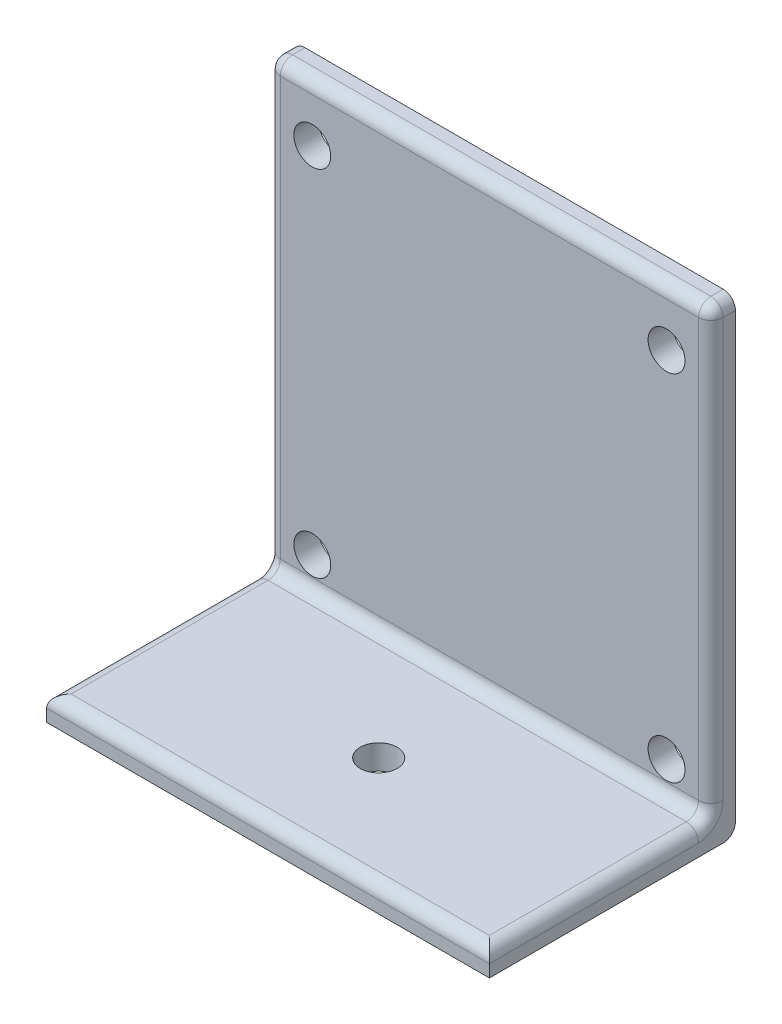
SolidWorks part; units mm, degrees
ref_plane "Front Plane" through (0, 0, 0) normal (0, 0, 1) x (1, 0, 0)
ref_plane "Top Plane" through (0, 0, 0) normal (0, 1, 0) x (1, 0, 0)
ref_plane "Right Plane" through (0, 0, 0) normal (1, 0, 0) x (0, 0, -1)
sketch "Sketch1" plane through (0, 0, 0) normal (0, 1, 0) x (1, 0, 0)
  line L1 (-18, -10) -> (18, -10)
  line L2 (-18, -10) -> (-18, 10)
  line L3 (-18, 10) -> (18, 10)
  line L4 (18, -10) -> (18, 10)
  line L5 (-18, -10) -> (18, 10) construction
  line L6 (-18, 10) -> (18, -10) construction
  point P0 (0, 0)
  dimension "D1" = 20
  dimension "D2" = 36
extrude "Boss-Extrude1" add sketch "Sketch1" along normal blind 2
sketch "Sketch2" plane through (0, 2, 0) normal (0, 1, 0) x (1, 0, 0)
  line L0 (18, -10) -> (18, 10) construction
  line L1 (-18, 10) -> (18, 10)
  line L2 (-18, 10) -> (-18, 8)
  line L3 (-18, 8) -> (18, 8)
  line L4 (18, 10) -> (18, 8)
  dimension "D1" = 2
extrude "Boss-Extrude2" add sketch "Sketch2" along normal blind 36
sketch "Sketch3" plane through (0, 0, -10) normal (0, 0, -1) x (-1, 0, 0)
  line L0 (-18, 38) -> (-18, 0) construction
  line L1 (-14.4, 4.6) -> (14.4, 4.6) construction
  line L2 (-14.4, 4.6) -> (-14.4, 33.4) construction
  line L3 (-14.4, 33.4) -> (14.4, 33.4) construction
  line L4 (14.4, 4.6) -> (14.4, 33.4) construction
  line L5 (-14.4, 4.6) -> (14.4, 33.4) construction
  line L6 (-14.4, 33.4) -> (14.4, 4.6) construction
  line L7 (-18, 38) -> (18, 38) construction
  circle A0 centre (-14.4, 33.4) radius 1.5
  circle A1 centre (14.4, 33.4) radius 1.5
  circle A2 centre (14.4, 4.6) radius 1.5
  circle A3 centre (-14.4, 4.6) radius 1.5
  point P0 (0, 19)
  point P7 (-18, 19)
  point P10 (0, 38)
  point P21 (0, 19)
  dimension "D2" = 3
  dimension "D1" = 28.8
  dimension "D3" = 4
extrude "Cut-Extrude1" cut sketch "Sketch3" against normal up to next
sketch "Sketch4" plane through (0, 2, 0) normal (0, 1, 0) x (1, 0, 0)
  line L4 (18, 8) -> (-18, 8)
  line L5 (-18, 8) -> (-18, -10)
  line L6 (-18, -10) -> (18, -10)
  line L7 (18, -10) -> (18, 8)
  line L8 (18, 8) -> (-18, 8)
  line L9 (-18, 8) -> (-18, -10)
  line L10 (-18, -10) -> (18, -10)
  line L11 (18, -10) -> (18, 8)
  circle A0 centre (0, -1) radius 1.5
  point P6 (-18, -1)
  point P7 (0, -10)
  dimension "D2" = 3
  dimension "D1" = 0
extrude "Cut-Extrude3" cut sketch "Sketch4" against normal up to next contours A0 region at (0, 2, 1)
fillet "Fillet1" radius 1 10 edges at (-18, 2, 1) (18, 2, 1) (0, 2, 10) (0, 2, -8) (18, 20, -8) (0, 38, -8) (-18, 20, -8) (0, 0, -10) (18, 38, -9) (-18, 38, -9)
